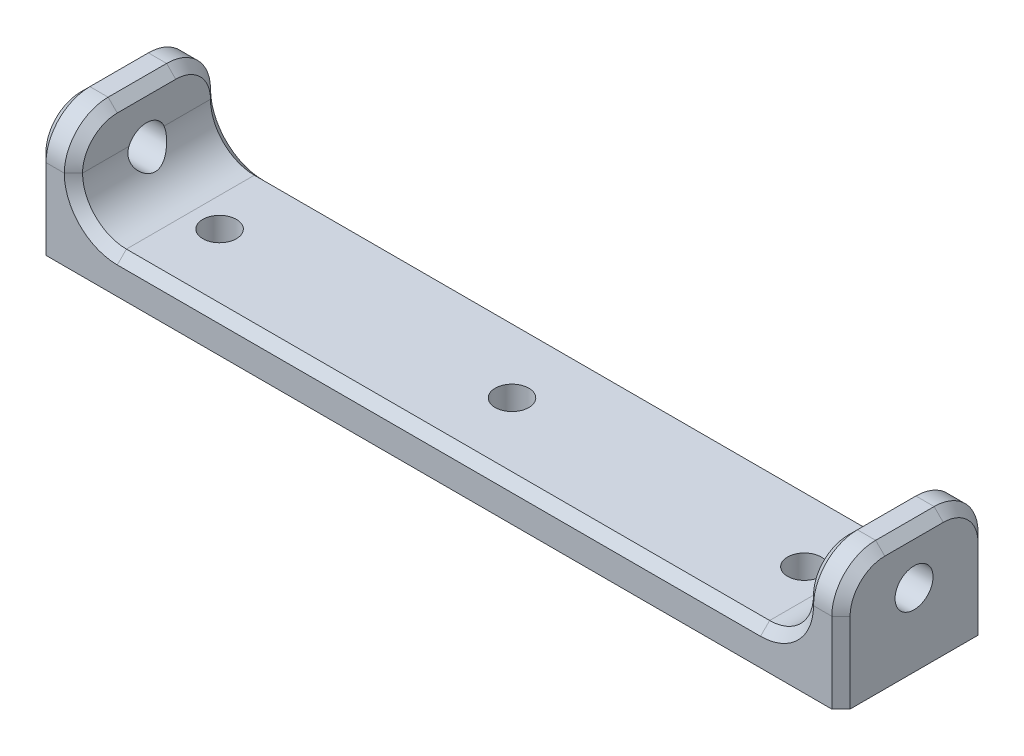
SolidWorks part; units mm, degrees
ref_plane "Front Plane" through (0, 0, 0) normal (0, 0, 1) x (1, 0, 0)
ref_plane "Top Plane" through (0, 0, 0) normal (0, 1, 0) x (1, 0, 0)
ref_plane "Right Plane" through (0, 0, 0) normal (1, 0, 0) x (0, 0, -1)
sketch "Sketch1" plane through (0, 0, 0) normal (0, 0, 1) x (1, 0, 0)
  line L0 (0, 0) -> (0, 21.59)
  line L1 (0, 21.59) -> (6.35, 21.59)
  line L2 (6.35, 21.59) -> (6.35, 6.35)
  line L3 (6.35, 6.35) -> (133.35, 6.35)
  line L4 (133.35, 6.35) -> (133.35, 21.59)
  line L5 (133.35, 21.59) -> (139.7, 21.59)
  line L6 (139.7, 21.59) -> (139.7, 0)
  line L7 (139.7, 0) -> (0, 0)
  dimension "D1" = 6.35
  dimension "D2" = 15.24
  dimension "D3" = 6.35
  dimension "D4" = 127
extrude "Boss-Extrude1" add sketch "Sketch1" along normal blind 25.4
fillet "Fillet1" radius 7.62 6 edges at (136.525, 21.59, 0) (136.525, 21.59, 25.4) (3.175, 21.59, 0) (3.175, 21.59, 25.4) (133.35, 6.35, 12.7) (6.35, 6.35, 12.7)
sketch "Sketch2" plane through (0, 6.35, 0) normal (0, 1, 0) x (1, 0, 0)
  line L0 (69.85, 0) -> (69.85, -25.4) construction
  line L1 (125.73, -25.4) -> (13.97, -25.4) construction
  line L2 (125.73, 0) -> (13.97, 0) construction
  circle A0 centre (69.85, -12.7) radius 2.921
  circle A1 centre (120.65, -12.7) radius 2.921
  circle A2 centre (19.05, -12.7) radius 2.921
  dimension "D1" = 5.842
  dimension "D2" = 50.8
  dimension "D3" = 50.8
extrude "Cut-Extrude1" cut sketch "Sketch2" against normal through all
chamfer "Chamfer1" distance 1.5875 angle 45 22 edges at (0, 6.985, 25.4) (0, 19.3582, 23.1682) (0, 21.59, 12.7) (0, 19.3582, 2.2318) (0, 6.985, 0) (139.7, 6.985, 25.4) (139.7, 6.985, 0) (139.7, 19.3582, 2.2318) (139.7, 21.59, 12.7) (139.7, 19.3582, 23.1682) (133.35, 19.3582, 23.1682) (133.35, 21.59, 12.7) (133.35, 19.3582, 2.2318) (131.1182, 8.5818, 0) (69.85, 6.35, 0) (8.5818, 8.5818, 0) (6.35, 19.3582, 2.2318) (6.35, 21.59, 12.7) (6.35, 19.3582, 23.1682) (8.5818, 8.5818, 25.4) (69.85, 6.35, 25.4) (131.1182, 8.5818, 25.4)
sketch "Sketch3" plane through (139.7, 0, 0) normal (1, 0, 0) x (0, 0, -1)
  line L0 (-12.7, 0) -> (-12.7, 20.0025) construction
  line L1 (-23.8125, 0) -> (-1.5875, 0) construction
  line L2 (-7.62, 20.0025) -> (-17.78, 20.0025) construction
  circle A0 centre (-12.7, 12.7) radius 3.302
  dimension "D1" = 6.604
  dimension "D2" = 12.7
extrude "Cut-Extrude2" cut sketch "Sketch3" against normal through all
